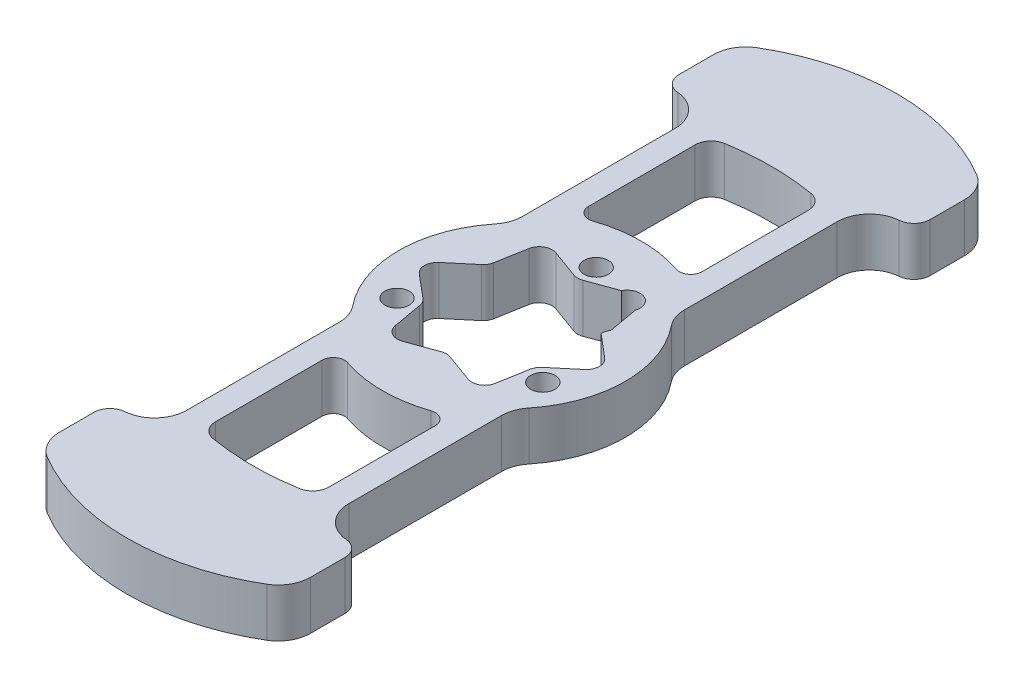
SolidWorks part; units mm, degrees
material "AISI 4340 Steel, annealed"
ref_plane "Front Plane" through (0, 0, 0) normal (0, 0, 1) x (1, 0, 0)
ref_plane "Top Plane" through (0, 0, 0) normal (0, 1, 0) x (1, 0, 0)
ref_plane "Right Plane" through (0, 0, 0) normal (1, 0, 0) x (0, 0, -1)
sketch "Sketch1" plane through (0, 0, 0) normal (0, 1, 0) x (1, 0, 0)
  line L0 (0, 0) -> (-15.875, 0) construction
  line L2 (-15.875, 47.8891) -> (-15.875, 17.9605)
  line L4 (15.875, 47.8891) -> (15.875, 17.9605)
  line L5 (-15.875, 50.8) -> (15.875, -50.8) construction
  line L6 (-15.875, -50.8) -> (15.875, 50.8) construction
  line L7 (6.4359, 15.0359) -> (0.8792, 13.0191)
  line L8 (-0.8666, 13.0145) -> (-6.4359, 15.0359)
  line L9 (-9.8035, 13.0916) -> (-10.8376, 7.2577)
  line L10 (-11.7042, 5.7568) -> (-16.2394, 1.9443)
  line L11 (-16.2394, -1.9443) -> (-11.7042, -5.7568)
  line L12 (-10.8376, -7.2577) -> (-9.8035, -13.0916)
  line L13 (-6.4359, -15.0359) -> (-0.8597, -13.012)
  line L14 (0.8724, -13.0166) -> (6.4359, -15.0359)
  line L15 (9.8035, -13.0916) -> (10.8376, -7.2577)
  line L16 (11.7042, -5.7568) -> (16.2394, -1.9443)
  line L17 (16.2394, 1.9443) -> (11.7042, 5.7568)
  line L18 (12.1466, 7.2577) -> (11.1125, 13.0917)
  line L19 (0.0067, 12.8621) -> (0.0067, -12.8621) construction
  line L20 (-17.145, 0) -> (12.065, 0) construction
  line L21 (15.875, -17.9605) -> (15.875, -47.8891)
  line L22 (-15.875, -17.9605) -> (-15.875, -47.8891)
  line L23 (-24.6267, -57.3827) -> (-24.6267, -64.1355)
  line L25 (24.6267, -57.3827) -> (24.6267, -64.1355)
  line L27 (-24.6267, 57.3827) -> (-24.6267, 64.1355)
  line L28 (24.6267, 57.3827) -> (24.6267, 64.1355)
  line L29 (-15.875, 41.3545) -> (-11.1125, 41.3545) construction
  line L30 (15.875, 36.8989) -> (11.1125, 36.8989) construction
  line L31 (-11.1125, 26.1528) -> (-11.1125, 47.0191)
  line L32 (11.1125, 47.0191) -> (11.1125, 26.1528)
  line L33 (-22.225, 0) -> (75.6572, 0) construction
  line L34 (11.1125, -47.0191) -> (11.1125, -26.1528)
  line L35 (-11.1125, -26.1528) -> (-11.1125, -47.0191)
  arc A2 (21.5119, 69.5996) -> (-21.5119, 69.5996) centre (0, 33.2669) ccw
  arc A3 (21.5119, -69.5996) -> (-21.5119, -69.5996) centre (0, -33.2669) cw
  arc A7 (-15.875, 47.8891) -> (-21.7095, 54.2182) centre (-22.225, 47.8891) ccw
  arc A8 (15.875, 47.8891) -> (21.7095, 54.2182) centre (22.225, 47.8891) cw
  arc A9 (-21.7095, -54.2182) -> (-15.875, -47.8891) centre (-22.225, -47.8891) ccw
  arc A10 (21.7095, -54.2182) -> (15.875, -47.8891) centre (22.225, -47.8891) cw
  circle A11 centre (-14.2981, -8.255) radius 2.3813
  circle A12 centre (0, 16.51) radius 2.3813
  circle A13 centre (14.2981, -8.255) radius 2.3813
  arc A14 (11.1125, 13.0917) -> (6.4359, 15.0359) centre (8.6984, 13.8815) ccw
  arc A15 (-0.8666, 13.0145) -> (0.8792, 13.0191) centre (0, 15.4021) ccw
  arc A16 (-6.4359, 15.0359) -> (-9.8035, 13.0916) centre (-7.3025, 12.6483) ccw
  arc A17 (-11.7042, 5.7568) -> (-10.8376, 7.2577) centre (-13.3386, 7.7011) ccw
  arc A18 (-16.2394, 1.9443) -> (-16.2394, -1.9443) centre (-14.605, 0) ccw
  arc A19 (-10.8376, -7.2577) -> (-11.7042, -5.7568) centre (-13.3386, -7.7011) ccw
  arc A20 (-9.8035, -13.0916) -> (-6.4359, -15.0359) centre (-7.3025, -12.6483) ccw
  arc A21 (0.8724, -13.0166) -> (-0.8597, -13.012) centre (0, -15.4021) ccw
  arc A22 (6.4359, -15.0359) -> (9.8035, -13.0916) centre (7.3025, -12.6483) ccw
  arc A23 (11.7042, -5.7568) -> (10.8376, -7.2577) centre (13.3386, -7.7011) ccw
  arc A24 (16.2394, -1.9443) -> (16.2394, 1.9443) centre (14.605, 0) ccw
  arc A25 (12.1466, 7.2577) -> (11.7042, 5.7568) centre (14.2433, 5.824) ccw
  arc A26 (-17.2861, 13.9693) -> (-17.2861, -13.9693) centre (0, 0) ccw
  arc A27 (17.2861, -13.9693) -> (17.2861, 13.9693) centre (0, 0) ccw
  arc A28 (-17.2861, 13.9693) -> (-15.875, 17.9605) centre (-22.225, 17.9605) ccw
  arc A29 (-15.875, -17.9605) -> (-17.2861, -13.9693) centre (-22.225, -17.9605) ccw
  arc A30 (15.875, -17.9605) -> (17.2861, -13.9693) centre (22.225, -17.9605) cw
  arc A31 (15.875, 17.9605) -> (17.2861, 13.9693) centre (22.225, 17.9605) ccw
  arc A36 (-24.6267, 64.1355) -> (-21.5119, 69.5996) centre (-18.2767, 64.1355) cw
  arc A37 (24.6267, 64.1355) -> (21.5119, 69.5996) centre (18.2767, 64.1355) ccw
  arc A38 (-24.6267, -64.1355) -> (-21.5119, -69.5996) centre (-18.2767, -64.1355) ccw
  arc A39 (21.5119, -69.5996) -> (24.6267, -64.1355) centre (18.2767, -64.1355) ccw
  arc A40 (-21.7095, -54.2182) -> (-24.6267, -57.3827) centre (-21.4517, -57.3827) ccw
  arc A41 (24.6267, -57.3827) -> (21.7095, -54.2182) centre (21.4517, -57.3827) ccw
  arc A42 (-21.7095, 54.2182) -> (-24.6267, 57.3827) centre (-21.4517, 57.3827) cw
  arc A43 (21.7095, 54.2182) -> (24.6267, 57.3827) centre (21.4517, 57.3827) ccw
  arc A44 (8.1747, 24.0486) -> (-8.1747, 24.0486) centre (0, 0) ccw construction
  arc A46 (-8.466, 50.1498) -> (8.466, 50.1498) centre (0, 0) cw
  arc A47 (-8.1747, 24.0486) -> (8.1747, 24.0486) centre (0, 0) cw
  arc A49 (8.466, 50.1498) -> (-8.466, 50.1498) centre (0, 0) ccw construction
  arc A50 (-11.1125, 47.0191) -> (-8.466, 50.1498) centre (-7.9375, 47.0191) cw
  arc A51 (11.1125, 47.0191) -> (8.466, 50.1498) centre (7.9375, 47.0191) ccw
  arc A52 (-11.1125, 26.1528) -> (-8.1747, 24.0486) centre (-8.89, 26.1528) ccw
  arc A53 (8.1747, 24.0486) -> (11.1125, 26.1528) centre (8.89, 26.1528) ccw
  arc A54 (8.1747, -24.0486) -> (11.1125, -26.1528) centre (8.89, -26.1528) cw
  arc A55 (-8.1747, -24.0486) -> (8.1747, -24.0486) centre (0, 0) ccw
  arc A56 (-11.1125, -26.1528) -> (-8.1747, -24.0486) centre (-8.89, -26.1528) cw
  arc A57 (-11.1125, -47.0191) -> (-8.466, -50.1498) centre (-7.9375, -47.0191) ccw
  arc A58 (-8.466, -50.1498) -> (8.466, -50.1498) centre (0, 0) ccw
  arc A59 (11.1125, -47.0191) -> (8.466, -50.1498) centre (7.9375, -47.0191) cw
  point P0 (0, 0)
  point P22 (-15.875, 56.6393)
  point P27 (-15.875, -56.6393)
  point P86 (15.875, -15.5543)
  point P91 (-49.1991, 36.1422)
  point P94 (49.1991, 36.1422)
  point P97 (-49.1991, -36.1422)
  point P100 (49.1991, -36.1422)
  dimension "D3" = 6.35
  dimension "D4" = 6.35
  dimension "D5" = 6.35
  dimension "D6" = 6.35
  dimension "D7" = 44.45
  dimension "D8" = 6.35
  dimension "D9" = 6.35
  dimension "D10" = 6.35
  dimension "D11" = 6.35
  dimension "D12" = 6.35
  dimension "D13" = 6.35
  dimension "D14" = 6.35
  dimension "D15" = 6.35
  dimension "D16" = 3.175
  dimension "D17" = 3.175
  dimension "D18" = 3.175
  dimension "D19" = 3.175
  dimension "D20" = 50.8
  dimension "D23" = 3.175
  dimension "D24" = 3.175
  dimension "D25" = 2.2225
  dimension "D26" = 2.2225
  dimension "D1" = 101.6
  dimension "D2" = 31.75
  dimension "D21" = 4.7625
  dimension "D22" = 4.7625
extrude "Boss-Extrude1" add sketch "Sketch1" along normal blind 9.525
